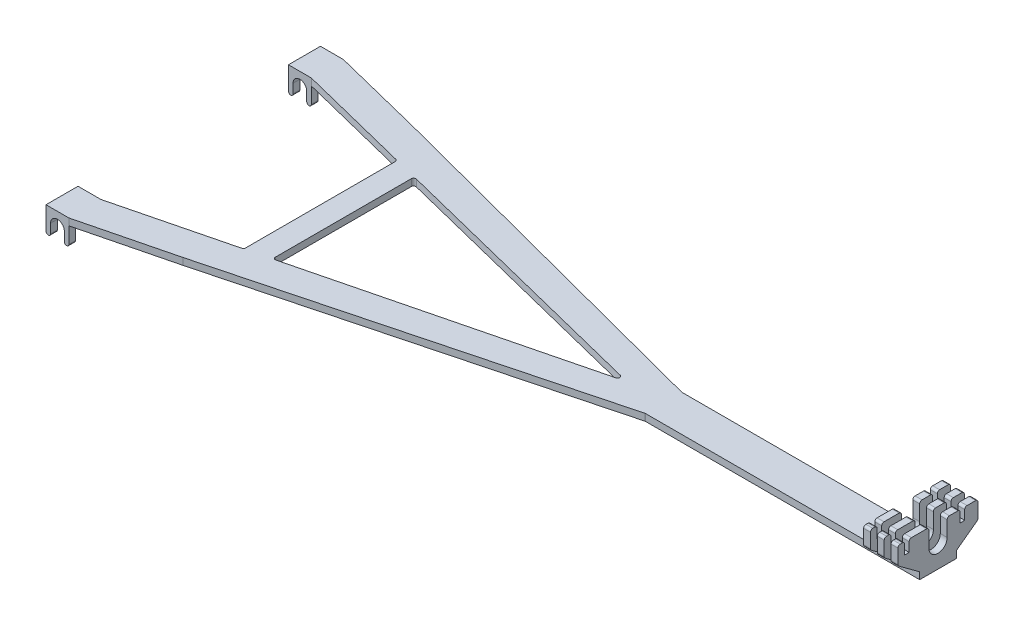
SolidWorks part; units mm, degrees
ref_plane "Front Plane" through (0, 0, 0) normal (0, 0, 1) x (1, 0, 0)
ref_plane "Top Plane" through (0, 0, 0) normal (0, 1, 0) x (1, 0, 0)
ref_plane "Right Plane" through (0, 0, 0) normal (1, 0, 0) x (0, 0, -1)
sketch "Sketch1" plane through (0, 0, 0) normal (0, 1, 0) x (1, 0, 0)
  line L0 (-450, 300) -> (-400, 300)
  line L1 (-400, 300) -> (-200, 250)
  line L2 (-200, 250) -> (200, 250) construction
  line L3 (200, 250) -> (600, 40) construction
  line L4 (600, 40) -> (1200, 40)
  line L5 (-450, -300) -> (-400, -300)
  line L6 (-400, -300) -> (-200, -250)
  line L7 (-200, -250) -> (200, -250) construction
  line L8 (200, -250) -> (600, -40) construction
  line L9 (600, -40) -> (1200, -40)
  line L10 (600, 40) -> (600, -40) construction
  line L11 (200, -250) -> (200, 250) construction
  line L12 (-200, 250) -> (-200, -250) construction
  line L13 (-400, -300) -> (-400, 300) construction
  line L14 (0, 0) -> (200, 0) construction
  line L15 (0, 250) -> (0, 0) construction
  line L16 (1200, 40) -> (1200, -40)
  line L17 (-450, 300) -> (-450, -300)
  line L18 (600, 0) -> (200, 0) construction
  line L19 (-450, 0) -> (-400, 0) construction
  line L20 (-400, 0) -> (-200, 0) construction
  line L21 (-200, 0) -> (0, 0) construction
  line L22 (-200, 250) -> (600, 40)
  line L23 (600, -40) -> (-200, -250)
  dimension "D1" = 600
  dimension "D2" = 200
  dimension "D3" = 50
  dimension "D4" = 400
  dimension "D5" = 500
  dimension "D6" = 80
  dimension "D7" = 600
  dimension "D8" = 400
extrude "Boss-Extrude1" add sketch "Sketch1" along normal blind 15
sketch "Sketch2" plane through (0, 0, 0) normal (0, 0, 1) x (1, 0, 0)
  line L0 (-450, 0) -> (-450, -40)
  line L1 (-450, -40) -> (-400, -40)
  line L2 (-400, -40) -> (-400, 0)
  line L3 (-400, 0) -> (-200, 0) construction
  line L4 (-400, 0) -> (-450, 0)
  line L5 (-440, -15) -> (-440, -40)
  line L6 (-410, -15) -> (-410, -40)
  line L7 (-425, 0) -> (-425, -15) construction
  circle A0 centre (-425, -15) radius 15
  point P13 (-403.2583, -61.8861)
  point P15 (0, 0)
  point P17 (-425, -25.2493)
  dimension "D1" = 30
  dimension "D2" = 40
extrude "Boss-Extrude2" add sketch "Sketch2" along normal up to surface and the other way up to surface contours L4 L7 A0 L6 L1 L2 | L7 L4 L0 L1 L5 A0 up to face at (-425, 7.5, 300) other way up to face at (-425, 7.5, -300)
sketch "Sketch4" plane through (0, 0, 0) normal (0, 1, 0) x (1, 0, 0)
  line L0 (-450, 230) -> (-400, 230)
  line L1 (-450, 300) -> (-450, -300) construction
  line L2 (-400, 230) -> (-150, 167.5)
  line L3 (-150, 167.5) -> (-150, -167.5)
  line L4 (-150, -167.5) -> (-400, -230)
  line L5 (-400, -230) -> (-450, -230)
  line L6 (-400, 230) -> (-400, -230) construction
  line L7 (-200, 250) -> (-200, -250) construction
  line L9 (-200, 0) -> (-150, 0) construction
  line L10 (-400, -230) -> (-400, -300) construction
  line L11 (-400, -300) -> (-200, -250) construction
  line L12 (-450, 230) -> (-450, -230)
  line L14 (-200, 250) -> (-400, 300) construction
  line L15 (-100, 155) -> (-100, -155)
  line L16 (-100, -155) -> (520, 0)
  line L17 (520, 0) -> (-100, 155)
  line L18 (520, 0) -> (-100, 0) construction
  dimension "D1" = 460
  dimension "D2" = 300
  dimension "D3" = 50
extrude "Cut-Extrude2" cut sketch "Sketch4" against normal through all both and the other way through all
sketch "Sketch5" plane through (0, 0, 0) normal (1, 0, 0) x (0, 0, -1)
  line L0 (-300, 0) -> (-230, 0) construction
  line L1 (-285, 0) -> (-245, 0)
  line L2 (-285, 0) -> (-285, -40)
  line L3 (-285, -40) -> (-245, -40)
  line L4 (-245, 0) -> (-245, -40)
  line L5 (-300, -40) -> (-230, -40) construction
  line L6 (230, 0) -> (300, 0) construction
  line L7 (245, 0) -> (285, 0)
  line L8 (245, 0) -> (245, -40)
  line L9 (245, -40) -> (285, -40)
  line L10 (285, 0) -> (285, -40)
  line L11 (230, -40) -> (300, -40) construction
  line L12 (-300, 0) -> (-300, -40) construction
  line L13 (230, -40) -> (230, 0) construction
  line L14 (300, 0) -> (300, -40) construction
  dimension "D1" = 15
  dimension "D2" = 15
  dimension "D3" = 15
  dimension "D4" = 15
extrude "Cut-Extrude3" cut sketch "Sketch5" against normal through all
sketch "Sketch7" plane through (1200, 0, 0) normal (1, 0, 0) x (0, 0, -1)
  line L1 (-40, 15) -> (-87.5, 50)
  line L2 (-87.5, 50) -> (-87.5, 88.7)
  line L3 (-87.5, 88.7) -> (87.5, 88.7)
  line L4 (87.5, 88.7) -> (87.5, 50)
  line L5 (87.5, 50) -> (40, 15)
  line L7 (-40, 15) -> (40, 15)
  line L8 (-20, 50) -> (-20, 88.7)
  line L9 (87.5, 50) -> (-87.5, 50) construction
  line L10 (0, 88.7) -> (0, 50) construction
  line L11 (-20, 88.7) -> (20, 88.7)
  line L12 (0, 50) -> (0, 0) construction
  line L13 (20, 88.7) -> (20, 50)
  line L14 (-73, 88.7) -> (-63, 88.7)
  line L15 (-73, 88.7) -> (-73, 63.2)
  line L16 (-73, 63.2) -> (-63, 63.2)
  line L17 (-63, 88.7) -> (-63, 63.2)
  line L18 (48.5, 88.7) -> (58.5, 88.7)
  line L19 (48.5, 88.7) -> (48.5, 63.2)
  line L20 (48.5, 63.2) -> (58.5, 63.2)
  line L21 (58.5, 88.7) -> (58.5, 63.2)
  circle A0 centre (0, 50) radius 20
  dimension "D3" = 40
  dimension "D1" = 175
  dimension "D2" = 50
  dimension "D4" = 25.5
  dimension "D5" = 10
  dimension "D6" = 63
  dimension "D7" = 48.5
  dimension "D8" = 38.7
extrude "Boss-Extrude4" add sketch "Sketch7" against normal blind 75
sketch "Sketch8" plane through (0, 0, 0) normal (0, 0, 1) x (1, 0, 0)
  line L0 (1125, 88.7) -> (1200, 88.7) construction
  line L1 (1140, 88.7) -> (1185, 88.7)
  line L2 (1140, 88.7) -> (1140, 15)
  line L3 (1140, 15) -> (1185, 15)
  line L4 (1185, 88.7) -> (1185, 15)
  line L5 (1125, 15) -> (1200, 15) construction
  line L6 (1125, 50) -> (1125, 88.7) construction
  line L7 (1200, 50) -> (1200, 88.7) construction
  line L8 (1155, 88.7) -> (1170, 88.7) construction
  line L9 (1155, 88.7) -> (1170, 88.7)
  line L10 (1155, 88.7) -> (1155, 15)
  line L11 (1155, 15) -> (1170, 15)
  line L12 (1170, 88.7) -> (1170, 15)
  line L15 (1162.5, 50) -> (1162.5, 88.7) construction
  line L16 (1125, 50) -> (1200, 50) construction
  line L17 (1155, 88.7) -> (1170, 88.7) construction
  point P20 (1166.2591, 65.556)
  point P21 (1173.0637, 88.105)
  dimension "D1" = 15
  dimension "D2" = 15
  dimension "D3" = 15
extrude "Cut-Extrude4" cut sketch "Sketch8" against normal through all both and the other way through all contours L10 L1 L2 L3 | L1 L12 L3 L4
fillet "Fillet1" radius 5 53 edges at (1192.5, 50, 87.5) (1162.5, 50, 87.5) (1132.5, 50, 87.5) (1192.5, 50, -87.5) (1162.5, 50, -87.5) (1132.5, 50, -87.5) (1192.5, 88.7, -87.5) (1162.5, 88.7, -87.5) (1132.5, 88.7, -87.5) (1132.5, 88.7, -58.5) (1162.5, 88.7, -58.5) (1192.5, 88.7, -58.5) (1192.5, 88.7, -48.5) (1162.5, 88.7, -48.5) (1132.5, 88.7, -48.5) (1192.5, 88.7, -20) (1162.5, 88.7, -20) (1132.5, 88.7, -20) (1192.5, 88.7, 63) (1162.5, 88.7, 63) (1132.5, 88.7, 63) (1132.5, 88.7, 87.5) (1162.5, 88.7, 87.5) (1192.5, 88.7, 87.5) (1192.5, 88.7, 73) (1162.5, 88.7, 73) (1132.5, 88.7, 73) (1192.5, 88.7, 20) (1162.5, 88.7, 20) (1132.5, 88.7, 20) (600, 7.5, 40) (600, 7.5, -40) (520, 7.5, 0) (-440, -40, -292.5) (-440, -40, -237.5) (-400, -40, -292.5) (-400, -40, -237.5) (-450, -40, -237.5) (-410, -40, -237.5) (-450, -40, -292.5) (-410, -40, -292.5) (-150, 7.5, 167.5) (-100, 7.5, 155) (-150, 7.5, -167.5) (-100, 7.5, -155) (-450, -40, 237.5) (-410, -40, 237.5) (-440, -40, 237.5) (-400, -40, 237.5) (-450, -40, 292.5) (-440, -40, 292.5) (-400, -40, 292.5) (-410, -40, 292.5)
